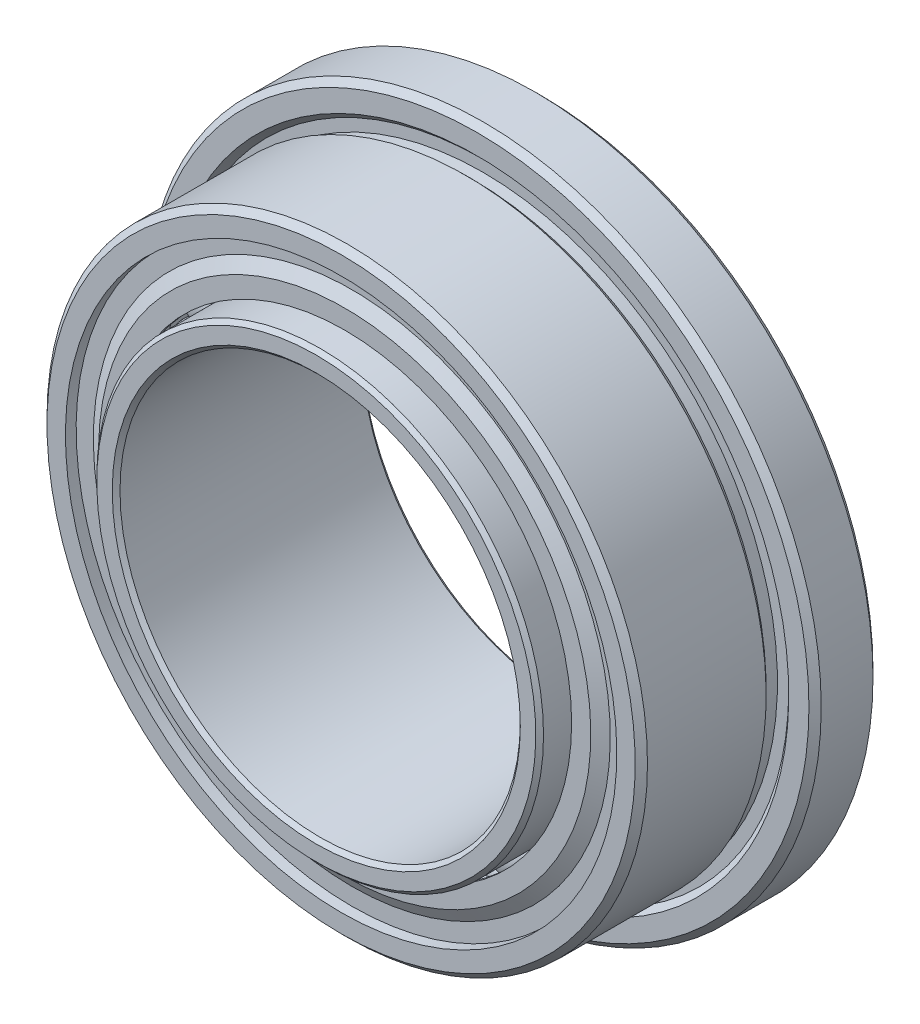
SolidWorks part; units mm, degrees
ref_plane "Front Plane" through (0, 0, 0) normal (0, 0, 1) x (1, 0, 0)
ref_plane "Top Plane" through (0, 0, 0) normal (0, 1, 0) x (1, 0, 0)
ref_plane "Right Plane" through (0, 0, 0) normal (1, 0, 0) x (0, 0, -1)
sketch "Sketch1" plane through (0, 0, 0) normal (1, 0, 0) x (0, 0, -1)
  line L0 (0, 4.7625) -> (0, -4.7625) construction
  line L1 (-1.5875, 4.7625) -> (1.5875, 4.7625) construction
  line L2 (0, 0) -> (1.5875, 0) construction
  line L3 (1.5875, 5.3594) -> (1.5875, -5.3594) construction
  line L4 (1.5875, -5.3594) -> (0.5715, -5.3594) construction
  line L5 (1.5875, 3.175) -> (0, 3.175) construction
  line L6 (1.5875, 3.175) -> (1.5875, -3.175) construction
  line L7 (0, 3.5433) -> (0, -3.5433) construction
  line L8 (-1.9812, 3.5433) -> (1.9812, 3.5433) construction
  point P16 (0, 0)
  point P19 (0, 3.5433)
  dimension "OD" = 9.525
  dimension "Width" = 3.175
  dimension "Flange Dia." = 10.7188
  dimension "Flange Thickness" = 1.016
  dimension "ID" = 6.35
  dimension "Inner Ring OD" = 7.0866
  dimension "Inner Ring Width" = 3.9624
sketch "Sketch2" plane through (0, 0, 0) normal (1, 0, 0) x (0, 0, -1)
  line L0 (1.5875, 5.3594) -> (0.5715, 5.3594)
  line L1 (0.5715, 5.3594) -> (0.5715, 4.9421)
  line L2 (0.3919, 4.7625) -> (-1.5875, 4.7625)
  line L3 (-1.5875, 4.7625) -> (-1.5875, 4.1783)
  line L4 (-1.5875, 4.1783) -> (-0.2381, 4.1783)
  line L5 (1.5875, 5.3594) -> (1.5875, -5.3594) construction
  line L6 (1.5875, 4.1783) -> (1.5875, 5.3594)
  line L7 (1.9812, 3.175) -> (-1.9812, 3.175)
  line L8 (-1.9812, 3.175) -> (-1.9812, 3.5433)
  line L9 (-1.9812, 3.5433) -> (-0.2381, 3.5433)
  line L10 (1.9812, 3.5433) -> (1.9812, 3.175)
  line L11 (0, 4.7625) -> (0, 3.175) construction
  line L12 (-0.3969, 3.8608) -> (0.3969, 3.8608) construction
  line L13 (0.2381, 4.1783) -> (1.5875, 4.1783)
  line L14 (0.2381, 3.5433) -> (1.9812, 3.5433)
  line L15 (0.5715, 4.9421) -> (0.6613, 4.8523)
  line L16 (0.6613, 4.8523) -> (0.6613, 4.6727)
  line L17 (0.6613, 4.6727) -> (0.4817, 4.6727)
  line L18 (0.4817, 4.6727) -> (0.3919, 4.7625)
  line L19 (0.5715, 4.7625) -> (0.6613, 4.6727) construction
  line L20 (0.6613, 4.8523) -> (0.4817, 4.6727) construction
  line L21 (0.3919, 4.7625) -> (0.5715, 4.7625) construction
  line L22 (0.5715, 4.7625) -> (0.5715, 4.9421) construction
  line L23 (-1.5875, 4.1783) -> (-1.5875, 3.5433) construction
  line L24 (1.5875, 3.175) -> (0, 3.175) construction
  line L25 (-1.5875, 3.8608) -> (-0.3969, 3.8608) construction
  circle A0 centre (0, 3.8608) radius 0.3969 construction
  arc A1 (-0.2381, 4.1783) -> (0.2381, 4.1783) centre (0, 3.8608) cw
  arc A2 (-0.2381, 3.5433) -> (0.2381, 3.5433) centre (0, 3.8608) ccw
  dimension "D1" = 1.5875
  dimension "Ball Dia." = 0.7937
  dimension "D2" = 135
  dimension "D3" = 0.254
  dimension "D4" = 0.635
  dimension "Outer Ring Thickness" = 0.5842
  dimension "Inner Wall" = 0.3683
revolve "Revolve1" add sketch "Sketch2" angle 360 about L2
fillet "Fillet1" radius 0.0974 3 edges at (0, -5.3594, -1.5875) (0, -5.3594, -0.5715) (0, -4.7625, 1.5875) profile chamfer
sketch "Sketch3" plane through (0, 0, 0) normal (0, 0, 1) x (1, 0, 0)
  line L0 (-3.175, 0) -> (3.175, 0) construction
  line L1 (-4.7625, 0) -> (4.7625, 0) construction
  point P5 (0, 0)
  dimension "ID2" = 6.35
  dimension "OD2" = 9.525
fillet "Fillet2" radius 0.0614 4 edges at (0, -3.5433, -1.9812) (0, -3.175, -1.9812) (0, -3.5433, 1.9812) (0, -3.175, 1.9812) profile chamfer
sketch "Sketch7" plane through (0, 0, 0) normal (0, 0, 1) x (1, 0, 0)
  line L0 (0, 4.2577) -> (0, 3.4639)
  line L1 (0, 5.3594) -> (0, -5.3594) construction
  line L2 (-0.44, 4.2577) -> (0, 0) construction
  line L3 (0, 0) -> (0.44, 4.2577) construction
  line L4 (0.44, 4.2577) -> (-0.44, 4.2577) construction
  circle A0 centre (0, 3.8608) radius 0.3969 construction
  circle A1 centre (0, 0) radius 4.2577 construction
  circle A2 centre (0, 0) radius 3.4639 construction
  arc A4 (0, 4.2577) -> (0, 3.4639) centre (0, 3.8608) ccw
  dimension "D1" = 11.8
revolve "Revolve3" add sketch "Sketch7" angle 360 about L0
pattern_circular "CirPattern3" count 27 over 360 about axis through (0, 0, 0) along (0, 0, -1) of bodies 107
sketch "Sketch8" plane through (0, 0, 0) normal (1, 0, 0) x (0, 0, -1)
  line L1 (-1.5875, 4.1783) -> (-1.3607, 4.1783)
  line L2 (-1.5875, 4.1783) -> (-1.5875, 4.373)
  line L3 (-1.5875, 4.373) -> (-1.3607, 4.373)
  line L4 (-1.3607, 4.1783) -> (-1.3607, 4.373)
  line L5 (1.5875, 4.1783) -> (1.3607, 4.1783)
  line L6 (1.5875, 4.1783) -> (1.5875, 4.373)
  line L7 (1.5875, 4.373) -> (1.3607, 4.373)
  line L8 (1.3607, 4.1783) -> (1.3607, 4.373)
  dimension "D1" = 0.1947
  dimension "D2" = 0.2268
revolve "Cut-Revolve1" cut sketch "Sketch8" angle 360 about L2
sketch "Sketch9" plane through (0, 0, 0) normal (1, 0, 0) x (0, 0, -1)
  line L0 (-1.3607, 4.373) -> (-1.3607, 4.0847)
  line L1 (-1.3607, 4.0847) -> (-1.4741, 3.8883)
  line L2 (-1.4741, 3.8883) -> (-1.4741, 3.6)
  line L3 (1.4741, 3.6) -> (1.4741, 3.5433) construction
  line L4 (1.3607, 4.373) -> (1.3607, 4.0847)
  line L5 (1.3607, 4.0847) -> (1.4741, 3.8883)
  line L6 (1.4741, 3.8883) -> (1.4741, 3.6)
  line L8 (-1.4174, 4.373) -> (-1.4174, 4.0999)
  line L9 (-1.4174, 4.0999) -> (-1.5308, 3.9035)
  line L10 (-1.5308, 3.9035) -> (-1.5308, 3.6)
  line L11 (-1.3607, 4.373) -> (-1.4174, 4.373)
  line L12 (-1.4741, 3.6) -> (-1.5308, 3.6)
  line L13 (1.4174, 4.373) -> (1.4174, 4.0999)
  line L14 (1.4174, 4.0999) -> (1.5308, 3.9035)
  line L15 (1.5308, 3.9035) -> (1.5308, 3.6)
  line L16 (1.3607, 4.373) -> (1.4174, 4.373)
  line L17 (1.4741, 3.6) -> (1.5308, 3.6)
  line L18 (-1.3607, 4.0847) -> (-1.3607, 4.7019) construction
  line L19 (1.3607, 4.0847) -> (1.3607, 4.373) construction
  line L20 (-1.4741, 4.1783) -> (-1.4741, 3.5433) construction
  line L22 (-1.4741, 3.6) -> (-1.4741, 3.5433) construction
  line L23 (-1.3607, 4.1783) -> (-1.5875, 4.1783) construction
  line L24 (-1.9812, 3.5433) -> (1.9812, 3.5433) construction
  dimension "D2" = 150
  dimension "D1" = 150
  dimension "D3" = 0.0567
  dimension "D4" = 0.0567
  dimension "D5" = 0.2268
revolve "Revolve4" add sketch "Sketch9" angle 360 about L2
ref_axis "Center Axis 1" through (0, 0, -1.7463) along (0, 0, 1)
ref_plane "Contact Plane 1" through (0, 0, -0.5715) normal (0, 0, 1) x (1, 0, 0)
move or copy body "Body-Move/Copy1" [suppressed]
equation "\"D3@Sketch2\"=\"Flange Thickness@Sketch1\"/4"
equation "\"D1@Fillet1\"=\"Outer Ring Thickness@Sketch2\"/6"
equation "\"ID2@Sketch3\" = \"ID@Sketch1\""
equation "\"OD2@Sketch3\" = \"OD@Sketch1\""
equation "\"D1@Fillet2\"=\"Inner Wall@Sketch2\"/6"
equation "\"D4@Sketch2\"=\"D1@Sketch2\"*.4"
equation "\"Ball Dia.@Sketch2\"= \"D1@Sketch2\" * .5"
equation "\"D1@CirPattern3\"=360/\"D1@Sketch7\"-4"
equation "\"D1@Sketch8\"=\"Outer Ring Thickness@Sketch2\"/3"
equation "\"D2@Sketch8\"=\"D1@Sketch2\"/7"
equation "\"D3@Sketch9\"=\"D5@Sketch9\"/4"
equation "\"D4@Sketch9\"=\"D5@Sketch9\"/4"
equation "\"D1@Sketch9\"=\"D2@Sketch9\""
